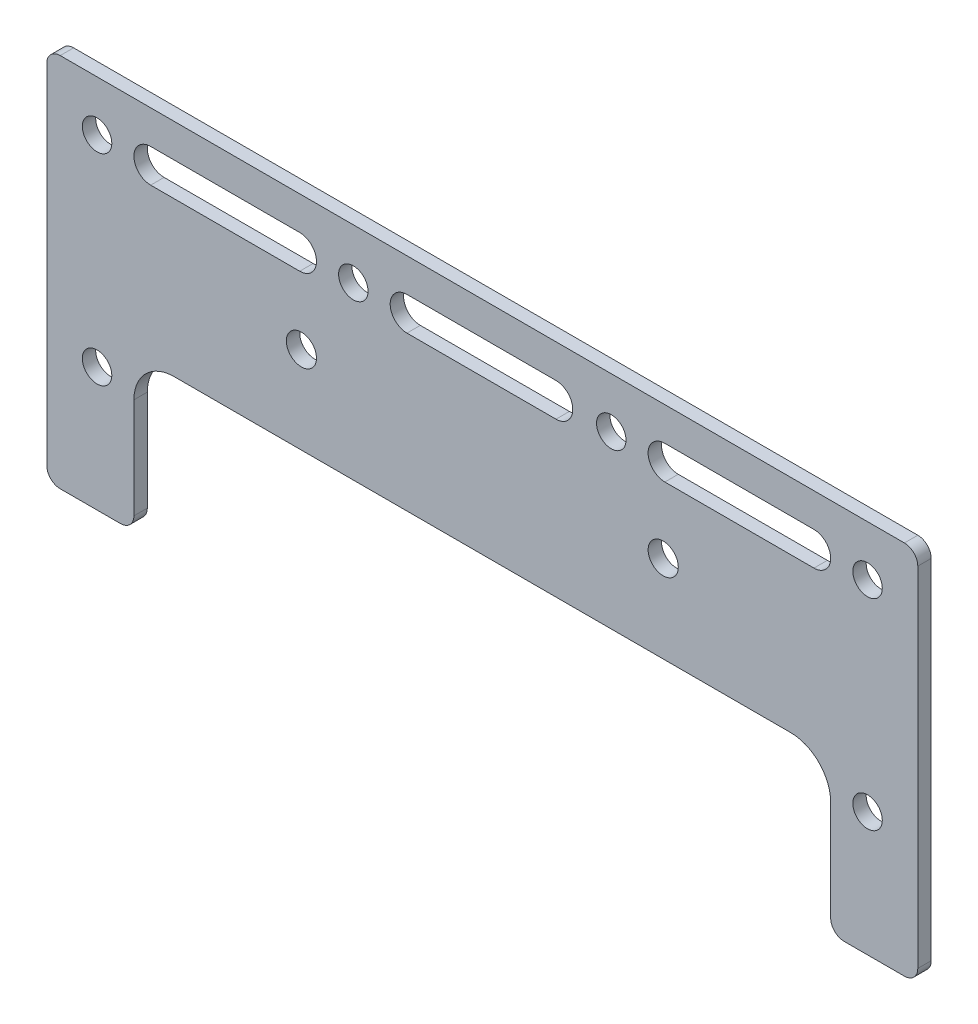
SolidWorks part; units mm, degrees
ref_plane "前视基准面" through (0, 0, 0) normal (0, 0, 1) x (1, 0, 0)
ref_plane "上视基准面" through (0, 0, 0) normal (0, 1, 0) x (1, 0, 0)
ref_plane "右视基准面" through (0, 0, 0) normal (1, 0, 0) x (0, 0, -1)
other "Configuration Table"
sketch "草图1" plane through (0, 0, 0) normal (0, 0, 1) x (1, 0, 0)
  line L0 (27.25, 18) -> (49.5, 18)
  line L1 (49.5, 23) -> (27.25, 23)
  line L2 (-11.25, 18) -> (11, 18)
  line L3 (11, 23) -> (-11.25, 23)
  line L4 (-49.5, 18) -> (-27.25, 18)
  line L5 (-27.25, 23) -> (-49.5, 23)
  line L6 (63, 28) -> (-63, 28)
  line L7 (-65, 26) -> (-65, -26)
  line L8 (-63, -28) -> (-54, -28)
  line L9 (-52, -26) -> (-52, -8)
  line L10 (-50, -6) -> (50, -6)
  line L11 (52, -8) -> (52, -26)
  line L12 (54, -28) -> (63, -28)
  line L13 (65, -26) -> (65, 26)
  circle A0 centre (-57.5, -9.5) radius 2.2
  circle A1 centre (-57.5, 20.5) radius 2.2
  circle A2 centre (19.25, 20.5) radius 2.2
  circle A3 centre (-19.25, 20.5) radius 2.2
  circle A4 centre (57.5, 20.5) radius 2.2
  circle A5 centre (57.5, -9.5) radius 2.2
  circle A6 centre (27, 2.5) radius 2.25
  circle A7 centre (-27, 2.5) radius 2.25
  arc A8 (27.25, 23) -> (27.25, 18) centre (27.25, 20.5) ccw
  arc A9 (49.5, 18) -> (49.5, 23) centre (49.5, 20.5) ccw
  arc A10 (-11.25, 23) -> (-11.25, 18) centre (-11.25, 20.5) ccw
  arc A11 (11, 18) -> (11, 23) centre (11, 20.5) ccw
  arc A12 (-49.5, 23) -> (-49.5, 18) centre (-49.5, 20.5) ccw
  arc A13 (-27.25, 18) -> (-27.25, 23) centre (-27.25, 20.5) ccw
  arc A14 (-63, 28) -> (-65, 26) centre (-63, 26) ccw
  arc A15 (-65, -26) -> (-63, -28) centre (-63, -26) ccw
  arc A16 (-54, -28) -> (-52, -26) centre (-54, -26) ccw
  arc A17 (-50, -6) -> (-52, -8) centre (-50, -8) ccw
  arc A18 (52, -8) -> (50, -6) centre (50, -8) ccw
  arc A19 (52, -26) -> (54, -28) centre (54, -26) ccw
  arc A20 (63, -28) -> (65, -26) centre (63, -26) ccw
  arc A21 (65, 26) -> (63, 28) centre (63, 26) ccw
extrude "凸台-拉伸1" add sketch "草图1" along normal blind 2
sketch "草图2" plane through (0, 0, 2) normal (0, 0, 1) x (1, 0, 0)
  line L0 (-52, -11) -> (52, -11)
  line L8 (63, 28) -> (-63, 28)
  line L9 (-65, 26) -> (-65, -26)
  line L10 (-63, -28) -> (-54, -28)
  line L11 (-52, -26) -> (-52, -8)
  line L12 (-50, -6) -> (50, -6)
  line L13 (52, -8) -> (52, -26)
  line L14 (54, -28) -> (63, -28)
  line L15 (65, -26) -> (65, 26)
  line L16 (63, 28) -> (-63, 28)
  line L17 (-65, 26) -> (-65, -26)
  line L18 (-63, -28) -> (-54, -28)
  line L19 (-52, -26) -> (-52, -8)
  line L20 (-50, -6) -> (50, -6)
  line L21 (52, -8) -> (52, -26)
  line L22 (54, -28) -> (63, -28)
  line L23 (65, -26) -> (65, 26)
  arc A8 (65, 26) -> (63, 28) centre (63, 26) ccw
  arc A9 (-63, 28) -> (-65, 26) centre (-63, 26) ccw
  arc A10 (-65, -26) -> (-63, -28) centre (-63, -26) ccw
  arc A11 (-54, -28) -> (-52, -26) centre (-54, -26) ccw
  arc A12 (-50, -6) -> (-52, -8) centre (-50, -8) ccw
  arc A13 (52, -8) -> (50, -6) centre (50, -8) ccw
  arc A14 (52, -26) -> (54, -28) centre (54, -26) ccw
  arc A15 (63, -28) -> (65, -26) centre (63, -26) ccw
  arc A16 (65, 26) -> (63, 28) centre (63, 26) ccw
  arc A17 (-63, 28) -> (-65, 26) centre (-63, 26) ccw
  arc A18 (-65, -26) -> (-63, -28) centre (-63, -26) ccw
  arc A19 (-54, -28) -> (-52, -26) centre (-54, -26) ccw
  arc A20 (-50, -6) -> (-52, -8) centre (-50, -8) ccw
  arc A21 (52, -8) -> (50, -6) centre (50, -8) ccw
  arc A22 (52, -26) -> (54, -28) centre (54, -26) ccw
  arc A23 (63, -28) -> (65, -26) centre (63, -26) ccw
  line M29 (-52, -26) -> (-52, -8)
  arc M30 (-52, -8) -> (-50, -6) centre (-50, -8) cw
  line M31 (-50, -6) -> (50, -6)
  arc M32 (50, -6) -> (52, -8) centre (50, -8) cw
  line M33 (52, -8) -> (52, -26)
  dimension "D2" = 5
  dimension "D1" = 0
extrude "凸台-拉伸2" add sketch "草图2" against normal blind 2 contours L0 M29 M33 M32 M31 M30 region at (0, -8.5068, 2)
sketch "草图3" plane through (0, 0, 2) normal (0, 0, 1) x (1, 0, 0)
  line L0 (-65, 8) -> (65, 8) construction
  line L1 (-65, 26) -> (-65, -26) construction
  line L2 (65, -26) -> (65, 26) construction
  line L3 (63, 28) -> (-63, 28) construction
  line L4 (-27, 2.5) -> (-27, 28)
  line L5 (27, 2.5) -> (27, 28)
  circle A0 centre (27, 2.5) radius 2.25 construction
  circle A1 centre (-27, 2.5) radius 2.25 construction
  circle A2 centre (27, 2.5) radius 2.25
  circle A3 centre (-27, 2.5) radius 2.25
  circle A4 centre (-27, 8) radius 2.25
  circle A5 centre (27, 8) radius 2.25
  dimension "D1" = 20
extrude "切除-拉伸1" cut sketch "草图3" against normal blind 23 contours L4 L0 A4 | L0 L4 A4 | L0 A4 L4 | A4 L0 L4 | A5 region at (-27.9549, 8.9549, 2) region at (-27.9549, 7.0451, 2) region at (-26.0451, 8.9549, 2) region at (-26.0451, 7.0451, 2)
extrude "凸台-拉伸3" add sketch "草图3<3>" against normal blind 2 contours A3 | A2
sketch "草图3<3>" plane through (0, 0, 2) normal (0, 0, 1) x (1, 0, 0) same geometry as "草图3"
sketch "草图5" plane through (0, 0, 2) normal (0, 0, 1) x (1, 0, 0)
  line L0 (-52, -11) -> (52, -11) construction
  line L1 (-52, -11) -> (52, -11)
  line L2 (-52, -11) -> (-52, -5)
  line L3 (-52, -5) -> (52, -5)
  line L4 (52, -5) -> (52, -11)
  dimension "D1" = 6
extrude "切除-拉伸2" cut sketch "草图5" against normal blind 24
fillet "圆角1" radius 6 2 edges at (52, -5, 1) (-52, -5, 1)
